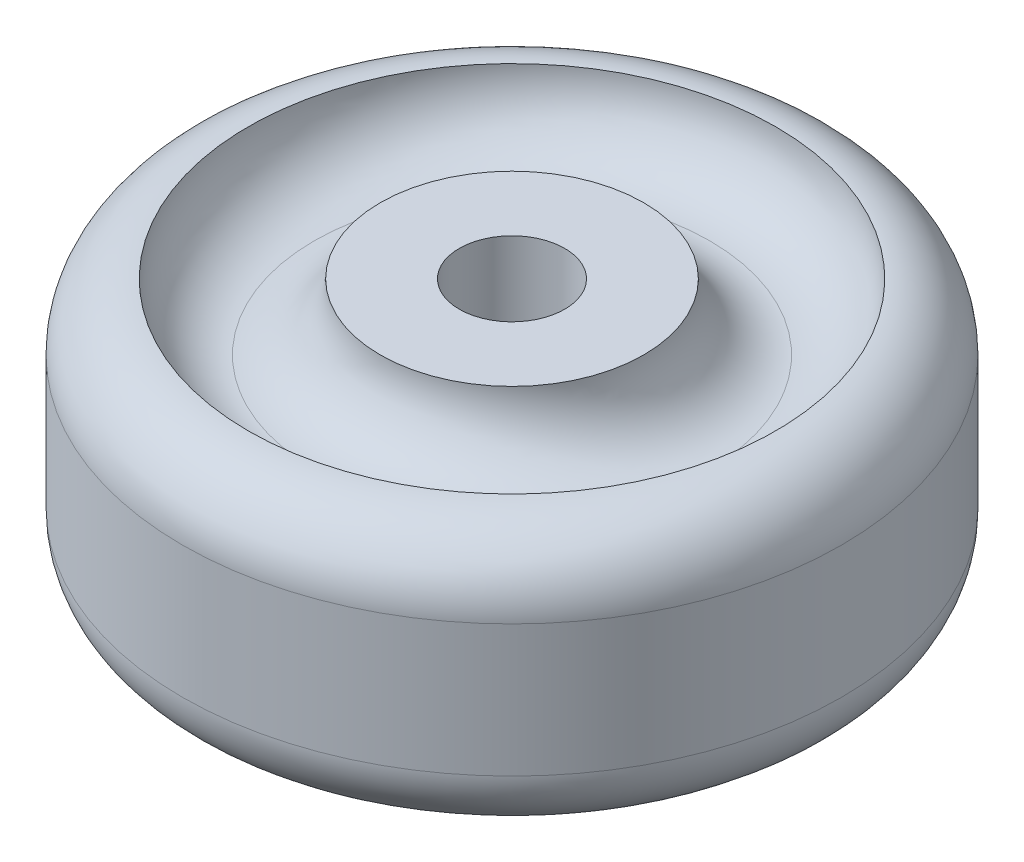
SolidWorks part; units mm, degrees
material "PVC Sztywny"
ref_plane "Płaszczyzna przednia" through (0, 0, 0) normal (0, 0, 1) x (1, 0, 0)
ref_plane "Płaszczyzna górna" through (0, 0, 0) normal (0, 1, 0) x (1, 0, 0)
ref_plane "Płaszczyzna prawa" through (0, 0, 0) normal (1, 0, 0) x (0, 0, -1)
sketch "Szkic1" plane through (0, 0, 0) normal (0, 1, 0) x (1, 0, 0)
  circle A0 centre (0, 0) radius 25
  dimension "D1" = 50
extrude "Dodanie-wyciągnięcie1" add sketch "Szkic1" along normal blind 10
sketch "Szkic2" plane through (0, 10, 0) normal (0, 1, 0) x (1, 0, 0)
  circle A0 centre (0, 0) radius 10
  circle A1 centre (0, 0) radius 20
  dimension "D1" = 20
  dimension "D2" = 40
extrude "Wytnij-wyciągnięcie1" cut sketch "Szkic2" against normal blind 5
fillet "Zaokrąglenie1" radius 5 2 edges at (0, 5, 20) (0, 5, 10)
sketch "Szkic3" plane through (0, 10, 0) normal (0, 1, 0) x (1, 0, 0)
  circle A0 centre (0, 0) radius 4
  dimension "D1" = 8
extrude "Wytnij-wyciągnięcie2" cut sketch "Szkic3" against normal through all and the other way through all
fillet "Zaokrąglenie2" radius 5 1 edges at (0, 10, 25)
mirror "Lustro1" about plane through (0, 0, 0) normal (0, 1, 0) of "Zaokrąglenie1", "Wytnij-wyciągnięcie2", "Wytnij-wyciągnięcie1", "Dodanie-wyciągnięcie1", "Zaokrąglenie2"
